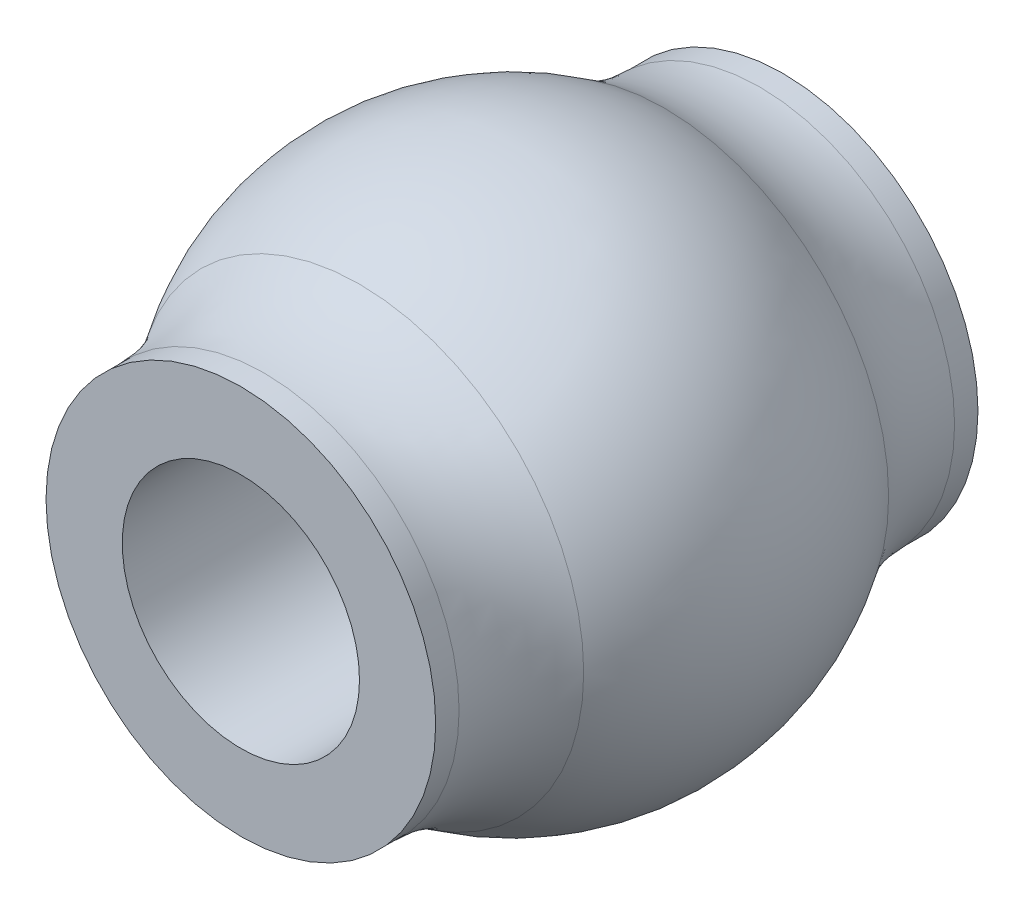
SolidWorks part; units mm, degrees
material "PLA"
ref_plane "Front Plane" through (0, 0, 0) normal (0, 0, 1) x (1, 0, 0)
ref_plane "Top Plane" through (0, 0, 0) normal (0, 1, 0) x (1, 0, 0)
ref_plane "Right Plane" through (0, 0, 0) normal (1, 0, 0) x (0, 0, -1)
sketch "Sketch1" plane through (0, 0, 0) normal (0, 1, 0) x (1, 0, 0)
  line L0 (8.875, 0.2811) -> (6, 0.2811)
  line L1 (6, 0.2811) -> (6, -5.2811)
  line L2 (6, -5.2811) -> (8.875, -5.2811)
  line L3 (6, 0.2811) -> (6, -5.2811) construction
  arc A0 (8.875, -5.2811) -> (8.875, 0.2811) centre (6, -2.5) ccw
revolve "Revolve1" add sketch "Sketch1" angle 360 about L3 reverse direction yes
sketch "Sketch2" plane through (0, 0, -0.2811) normal (0, 0, -1) x (-1, 0, 0)
  circle A0 centre (-6, 0) radius 2.875
extrude "Boss-Extrude1" add sketch "Sketch2" along normal blind 1.2189
sketch "Sketch3" plane through (0, 0, 5.2811) normal (0, 0, 1) x (1, 0, 0)
  circle A0 centre (6, 0) radius 2.875
extrude "Boss-Extrude2" add sketch "Sketch3" along normal blind 1.2189
sketch "Sketch4" plane through (0, 0, -1.5) normal (0, 0, -1) x (-1, 0, 0)
  circle A0 centre (-6, 0) radius 1.75
extrude "Cut-Extrude1" cut sketch "Sketch4" against normal through all
fillet "Fillet1" radius 2.5 2 edges at (8.875, 0, 5.2811) (3.125, 0, -0.2811) tangent propagation no
ref_plane "Plane1" through (0, 0, 2.5) normal (0, 0, -1) x (-1, 0, 0)
